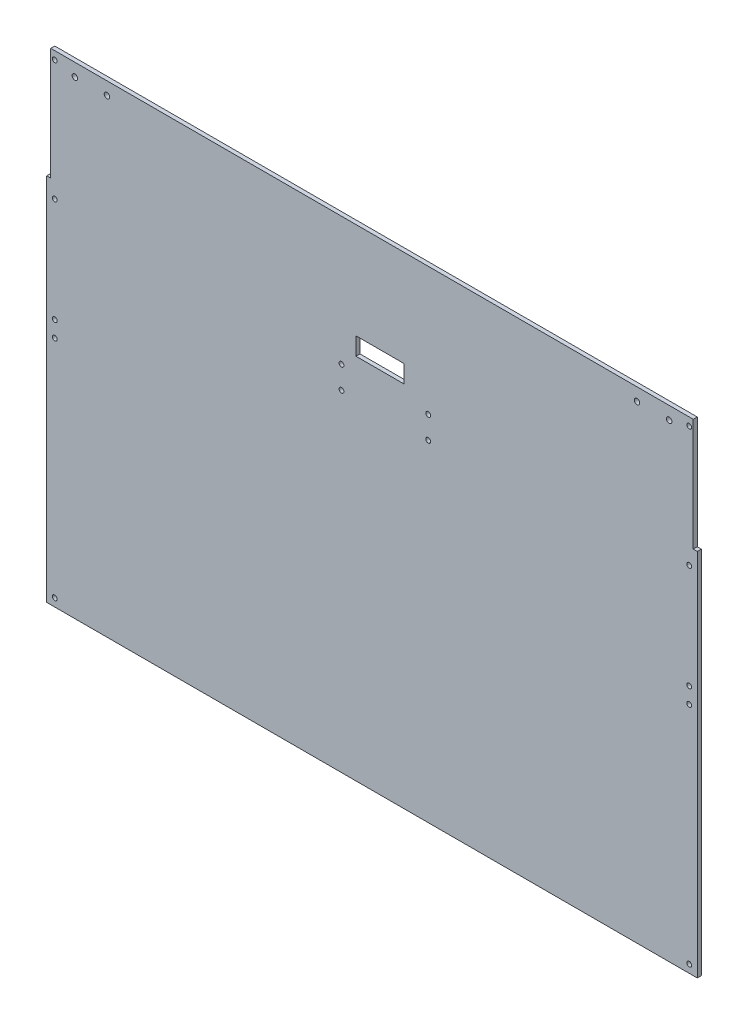
SolidWorks part; units mm, degrees
ref_plane "Front Plane" through (0, 0, 0) normal (0, 0, 1) x (1, 0, 0)
ref_plane "Top Plane" through (0, 0, 0) normal (0, 1, 0) x (1, 0, 0)
ref_plane "Right Plane" through (0, 0, 0) normal (1, 0, 0) x (0, 0, -1)
sketch "Sketch1" plane through (0, 0, 0) normal (0, 0, 1) x (1, 0, 0)
  line L1 (-254, -190.5) -> (254, -190.5)
  line L2 (-254, -190.5) -> (-254, 190.5)
  line L3 (-254, 190.5) -> (254, 190.5)
  line L4 (254, -190.5) -> (254, 190.5)
  line L5 (-254, -190.5) -> (254, 190.5) construction
  line L6 (-254, 190.5) -> (254, -190.5) construction
  point P0 (0, 0)
  dimension "D1" = 508
  dimension "D2" = 381
extrude "Boss-Extrude1" add sketch "Sketch1" along normal blind 3.175
sketch "Sketch3" plane through (0, 0, 3.175) normal (0, 0, 1) x (1, 0, 0)
  line L0 (254, 190.5) -> (-254, 190.5) construction
  line L1 (25.4, 100.33) -> (25.4, 114.3)
  line L2 (25.4, 100.33) -> (-12.7, 100.33)
  line L3 (-12.7, 100.33) -> (-12.7, 114.3)
  line L4 (25.4, 114.3) -> (-12.7, 114.3)
  line L5 (-254, 190.5) -> (-254, -190.5) construction
  point P4 (-12.3182, 122.7628)
  dimension "D1" = 76.2
  dimension "D2" = 13.97
  dimension "D3" = 241.3
  dimension "D4" = 38.1
extrude "Cut-Extrude2" cut sketch "Sketch3" against normal up to surface (3.175 mm away) up to face at (0, 0, 0)
sketch "Sketch2" plane through (0, 0, 3.175) normal (0, 0, 1) x (1, 0, 0)
  line L1 (254, 190.5) -> (-254, 190.5) construction
  line L2 (-254, -190.5) -> (254, -190.5) construction
  line L3 (250.825, 190.5) -> (250.825, -190.5) construction
  line L4 (254, -190.5) -> (254, 190.5) construction
  line L5 (-24.13, 89.1148) -> (44.45, 89.1148) construction
  line L6 (0, 0) -> (0, -50000) construction
  line L10 (254, 190.5) -> (-254, 190.5) construction
  line L11 (-24.13, 89.1148) -> (-24.13, 71.3348) construction
  line L12 (-24.13, 71.3348) -> (44.45, 71.3348) construction
  line L13 (44.45, 89.1148) -> (44.45, 71.3348) construction
  line L14 (-12.7, 114.3) -> (-12.7, 100.33) construction
  line L15 (-12.7, 100.33) -> (25.4, 100.33) construction
  circle A2 centre (250.825, 184.15) radius 1.905
  circle A3 centre (250.825, -184.15) radius 1.905
  circle A12 centre (-24.13, 89.1148) radius 1.905
  circle A13 centre (-24.13, 71.3348) radius 1.905
  circle A14 centre (44.45, 89.1148) radius 1.905
  circle A15 centre (44.45, 71.3348) radius 1.905
  circle A16 centre (-250.825, 184.15) radius 1.905
  circle A17 centre (-250.825, 88.9) radius 1.905
  circle A18 centre (250.825, 88.9) radius 1.905
  circle A19 centre (250.825, 6.35) radius 1.905
  circle A20 centre (250.825, -6.35) radius 1.905
  circle A21 centre (-250.825, 6.35) radius 1.905
  circle A22 centre (-250.825, -6.35) radius 1.905
  circle A23 centre (-250.825, -184.15) radius 1.905
  point P33 (0, -190.5)
  dimension "D3" = 11.2152
  dimension "D14" = 3.81
  dimension "D12" = 68.58
  dimension "D18" = 3.81
  dimension "D1" = 3.175
  dimension "D2" = 11.43
  dimension "D5" = 6.35
  dimension "D6" = 6.35
  dimension "D11" = 177.8
  dimension "D13" = 17.78
  dimension "D17" = 177.8
  dimension "D19" = 101.6
extrude "Cut-Extrude1" cut sketch "Sketch2" against normal blind 3.175
sketch "Sketch4" plane through (0, 0, 3.175) normal (0, 0, 1) x (1, 0, 0)
  line L0 (254, -190.5) -> (254, 190.5) construction
  line L1 (254, 101.6) -> (257.175, 101.6)
  line L2 (254, 101.6) -> (254, -190.5)
  line L3 (254, -190.5) -> (257.175, -190.5)
  line L4 (257.175, 101.6) -> (257.175, -190.5)
  line L5 (-254, -190.5) -> (254, -190.5) construction
  line L6 (254, 190.5) -> (-254, 190.5) construction
  line L7 (0, 190.5) -> (0, -190.5) construction
  line L8 (-254, -190.5) -> (-257.175, -190.5)
  line L9 (-254, 101.6) -> (-257.175, 101.6)
  line L10 (-254, 101.6) -> (-254, -190.5)
  line L11 (-257.175, 101.6) -> (-257.175, -190.5)
  dimension "D1" = 3.175
  dimension "D2" = 88.9
extrude "Boss-Extrude2" add sketch "Sketch4" against normal blind 3.175
sketch "Sketch5" plane through (0, 0, 0) normal (0, 0, -1) x (-1, 0, 0)
  line L0 (254, 190.5) -> (254, 101.6) construction
  line L1 (-254, 190.5) -> (254, 190.5) construction
  line L2 (-254, 101.6) -> (-254, 190.5) construction
  circle A0 centre (234.95, 180.34) radius 2.159
  circle A1 centre (209.55, 180.34) radius 2.159
  circle A2 centre (-234.95, 180.34) radius 2.159
  circle A3 centre (-209.55, 180.34) radius 2.159
  dimension "D3" = 4.318
  dimension "D1" = 19.05
  dimension "D2" = 44.45
  dimension "D4" = 10.16
  dimension "D5" = 19.05
  dimension "D6" = 44.45
extrude "Cut-Extrude3" cut sketch "Sketch5" against normal through all
